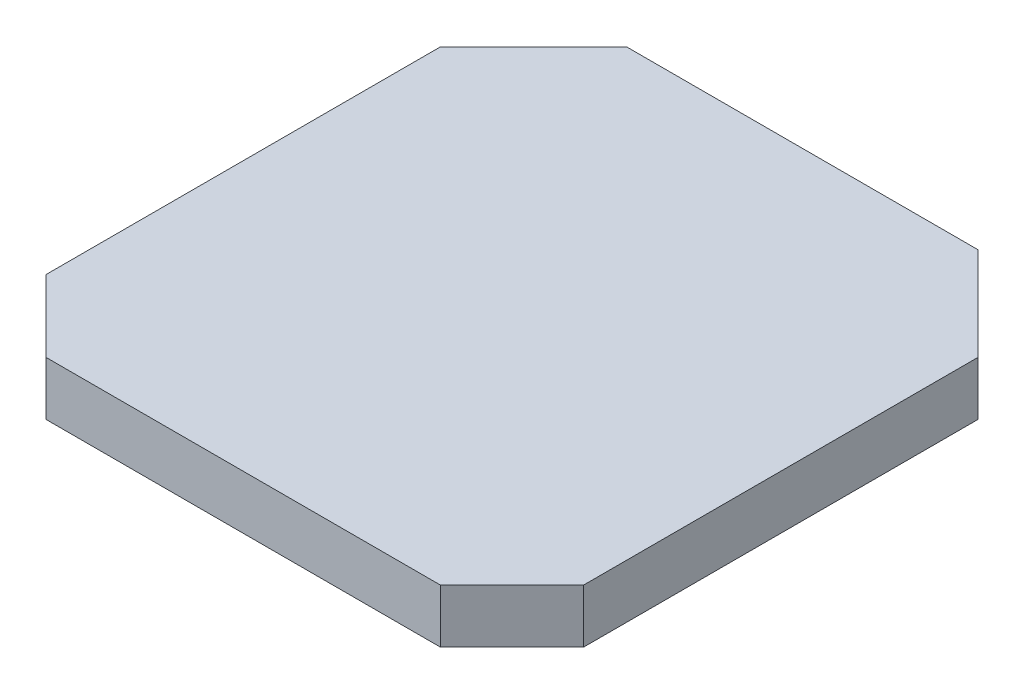
SolidWorks part; units mm, degrees
ref_plane "Front Plane" through (0, 0, 0) normal (0, 0, 1) x (1, 0, 0)
ref_plane "Top Plane" through (0, 0, 0) normal (0, 1, 0) x (1, 0, 0)
ref_plane "Right Plane" through (0, 0, 0) normal (1, 0, 0) x (0, 0, -1)
sketch "Sketch1" plane through (0, 0, 0) normal (0, 1, 0) x (1, 0, 0)
  line L0 (-37.5, 27.5) -> (-27.5, 37.5)
  line L1 (-27.5, 37.5) -> (27.5, 37.5)
  line L2 (-37.5, 27.5) -> (-37.5, -27.5)
  line L3 (-27.5, -37.5) -> (27.5, -37.5)
  line L4 (37.5, 27.5) -> (37.5, -27.5)
  line L5 (-37.5, 37.5) -> (37.5, -37.5) construction
  line L6 (-37.5, -37.5) -> (37.5, 37.5) construction
  line L7 (27.5, 37.5) -> (37.5, 27.5)
  line L8 (27.5, -37.5) -> (37.5, -27.5)
  line L9 (-37.5, -27.5) -> (-27.5, -37.5)
  point P0 (0, 0)
extrude "Boss-Extrude1" add sketch "Sketch1" along normal blind 7.5
ref_axis "Axis1" through (0, 7.875, 0) along (0, -1, 0)
sketch "Sketch2" plane through (0, 7.5, 0) normal (0, 1, 0) x (1, 0, 0)
  line L1 (-26.483, -36.483) -> (26.483, -36.483)
  line L8 (26.483, -36.483) -> (27.966, -35)
  line L9 (-27.966, -35) -> (-26.483, -36.483)
  line L13 (-25, -35) -> (25, -35)
  line L20 (-25, -35) -> (-27.966, -35)
  line L21 (25, -35) -> (27.966, -35)
  point P0 (0, 0)
  point P14 (0, 0)
sketch "Sketch8" plane through (0, 0, -37.5) normal (0, 0, -1) x (-1, 0, 0)
  line L0 (-27.5, 7.5) -> (27.5, 7.5) construction
  line L7 (-25, 3) -> (25, 3)
  line L9 (0, 7.5) -> (25, 3) construction
  line L10 (-25, 3) -> (0, 7.5) construction
  line L11 (-25, 7.5) -> (25, 7.5)
  line L13 (-25, 3) -> (-27.5, 3)
  line L15 (-25, 7.5) -> (-27.5, 7.5)
  line L16 (-27.5, 3) -> (-27.5, 7.5)
  line L17 (25, 3) -> (27.5, 3)
  line L19 (25, 7.5) -> (27.5, 7.5)
  line L20 (27.5, 3) -> (27.5, 7.5)
  point P0 (0, 7.5)
extrude "Boss-Extrude4" add sketch "Sketch8" along normal blind 3
chamfer "Chamfer7" distance 3 angle 45 1 edges at (0, 3, -40.5)
chamfer "Chamfer8" distance 3 angle 45 2 edges at (-27.5, 6.75, -40.5) (27.5, 6.75, -40.5)
